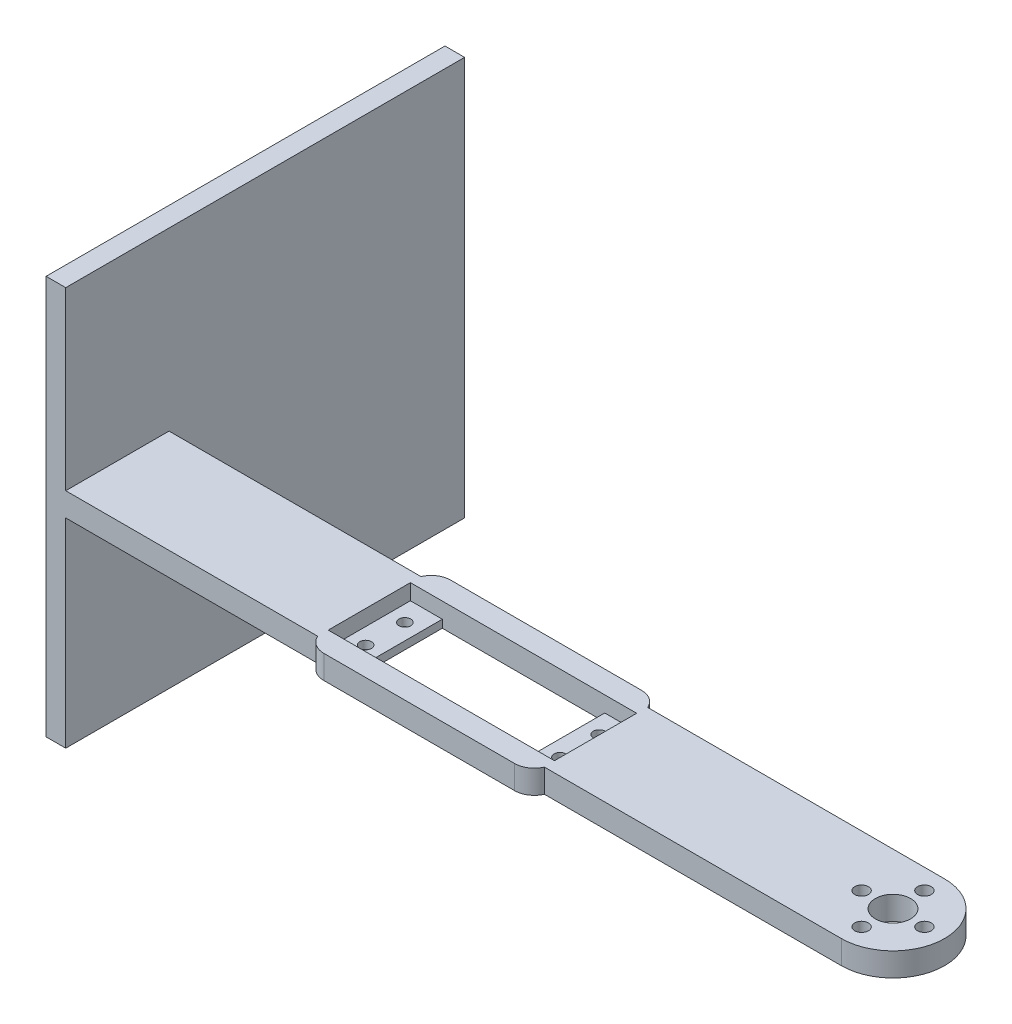
SolidWorks part; units mm, degrees
ref_plane "Front Plane" through (0, 0, 0) normal (0, 0, 1) x (1, 0, 0)
ref_plane "Top Plane" through (0, 0, 0) normal (0, 1, 0) x (1, 0, 0)
ref_plane "Right Plane" through (0, 0, 0) normal (1, 0, 0) x (0, 0, -1)
sketch "Sketch1" plane through (0, 0, 0) normal (0, 1, 0) x (1, 0, 0)
  line L0 (0, 0) -> (0, -8)
  line L3 (-144.1363, -13.1544) -> (-144.1363, 13.1544)
  line L4 (-104.5717, 5) -> (-104.5717, -5) construction
  line L5 (-83.8865, -10.7454) -> (-75.7569, -10.7454)
  line L6 (-129.3217, -5) -> (-79.8217, -5) construction
  line L7 (-129.3217, 5) -> (-79.8217, 5) construction
  line L12 (-83.8865, -10.7454) -> (-83.8865, 10.4665)
  line L13 (-83.8865, 10.4665) -> (-75.7569, 10.4665)
  line L14 (-75.7569, -10.7454) -> (-75.7569, 10.4665)
  line L15 (-83.8865, -10.7454) -> (-75.7569, 10.4665) construction
  line L16 (-83.8865, 10.4665) -> (-75.7569, -10.7454) construction
  line L17 (-125.2569, -10.7454) -> (-133.3865, -10.7454)
  line L18 (-133.3865, -10.7454) -> (-133.3865, 10.4665)
  line L19 (-125.2569, 10.4665) -> (-133.3865, 10.4665)
  line L20 (-125.2569, -10.7454) -> (-125.2569, 10.4665)
  line L21 (-75.7569, 10.4665) -> (-75.7569, -10.7454)
  line L22 (-75.7569, 10.4665) -> (-133.3865, 10.4665)
  line L23 (-75.7569, -10.7454) -> (-133.3865, -10.7454)
  line L24 (-133.3865, 10.4665) -> (-133.3865, -10.7454)
  line L25 (0, 13.1544) -> (-144.1363, 13.1544)
  line L26 (0, -13.1544) -> (-144.1363, -13.1544)
  line L27 (-144.1363, 13.1544) -> (-144.1363, -13.1544)
  line L28 (-144.1363, -13.1544) -> (-202.5563, -13.1544)
  line L29 (-144.1363, 13.1544) -> (-202.5563, 13.1544)
  line L30 (-202.5563, -13.1544) -> (-202.5563, 13.1544)
  line L31 (-202.5563, 0) -> (-197.5563, 0) construction
  line L32 (-202.5563, -13.1544) -> (-197.5563, -13.1544)
  line L33 (-202.5563, -13.1544) -> (-202.5563, 88.4456)
  line L34 (-197.5563, -13.1544) -> (-197.5563, 88.4456)
  line L35 (-202.5563, 88.4456) -> (-197.5563, 88.4456)
  circle A0 centre (0, 0) radius 4.5
  circle A1 centre (0, -8) radius 1.75
  circle A2 centre (-8, 0) radius 1.75
  circle A3 centre (0, 8) radius 1.75
  circle A4 centre (8, 0) radius 1.75
  circle A8 centre (-129.3217, 5) radius 1.5
  circle A9 centre (-129.3217, -5) radius 1.5
  circle A10 centre (-79.8217, 5) radius 1.5
  circle A11 centre (-79.8217, -5) radius 1.5
  arc A12 (0, -13.1544) -> (0, 13.1544) centre (0, 0) ccw
  arc A14 (-75.7569, -10.7454) -> (-73.3479, -13.1544) centre (-75.7569, -13.1544) cw
  arc A15 (-75.7569, 10.4665) -> (-73.0691, 13.1544) centre (-75.7569, 13.1544) ccw
  point P7 (13.1544, 0)
  point P14 (0, 0)
  point P19 (-79.8217, -0.1394)
  point P45 (-200.0563, 88.4456)
  dimension "D1" = 9
  dimension "D3" = 3.5
  dimension "D7" = 5
  dimension "D10" = 3
  dimension "D11" = 3
  dimension "D14" = 3
  dimension "D15" = 3
  dimension "D2" = 8
  dimension "D5" = 157.2907
  dimension "D6" = 58.42
  dimension "D8" = 101.6
  dimension "D12" = 49.5
  dimension "D13" = 49.5
  dimension "D16" = 10
  dimension "D4" = 4
extrude "Boss-Extrude1" add sketch "Sketch1" along normal blind 6 contours L34 L28 L3 L29 | L13 A15 L25 L3 L26 A14 L5 L23 L17 L18 L19 L22 | A15 L14 A14 L26 A12 L25 A1 A0 A2 A3 A4 region at (-170.8463, 0, 0) region at (-143.3785, 0, 0) region at (-34.0123, 0, 0.006)
extrude "Boss-Extrude2" add sketch "Sketch1<22>" along normal blind 2 contours L17 L20 L19 L18 A9 A8 | L5 L14 L13 L12 A11 A10 region at (-79.8217, 0, 0.1519) region at (-129.3217, 0, 0.1519)
sketch "Sketch1<22>" plane through (0, 0, 0) normal (0, 1, 0) x (1, 0, 0) same geometry as "Sketch1"
extrude "Boss-Extrude3" add sketch "Sketch1<23>" along normal blind 50.8 and the other way blind 50.8 contours L35 L33 L29 L34 | L28 L34 L29 L30 region at (-200.0563, 0, 0) region at (-200.0563, 0, -50.8)
sketch "Sketch1<23>" plane through (0, 0, 0) normal (0, 1, 0) x (1, 0, 0) same geometry as "Sketch1"
sketch "Sketch3" plane through (0, 6, 0) normal (0, 1, 0) x (1, 0, 0)
  line L0 (-133.3865, -10.7454) -> (-133.3865, -37.2112) construction
  line L1 (-75.7569, -10.7454) -> (-75.7569, -28.7695) construction
  line L2 (13.1544, 0) -> (-155.7689, 0) construction
  arc A0 (0, -13.1544) -> (0, 13.1544) centre (0, 0) ccw construction
sketch "Sketch4" plane through (0, 0, 13.1544) normal (0, 0, 1) x (1, 0, 0)
  line L0 (-133.384, 6) -> (-133.384, 0) construction
  line L1 (0, 6) -> (-197.5563, 6) construction
  line L2 (0, 0) -> (-197.5563, 0) construction
  line L3 (-75.635, 6) -> (-75.635, 0) construction
  line L5 (-133.384, 0) -> (-75.635, 0)
  line L6 (-133.384, 0) -> (-133.384, 6)
  line L7 (-133.384, 6) -> (-75.635, 6)
  line L8 (-75.635, 0) -> (-75.635, 6)
extrude "Boss-Extrude4" add sketch "Sketch4" along normal blind 3
fillet "Fillet2" radius 5 2 edges at (-75.635, 3, 16.1544) (-133.384, 3, 16.1544)
ref_plane "Plane1" through (0, 0, 0) normal (0, 0, -1) x (-1, 0, 0)
mirror "Mirror1" about plane through (0, 0, 0) normal (0, 0, -1) of "Boss-Extrude1", "Fillet2", "Boss-Extrude4"
